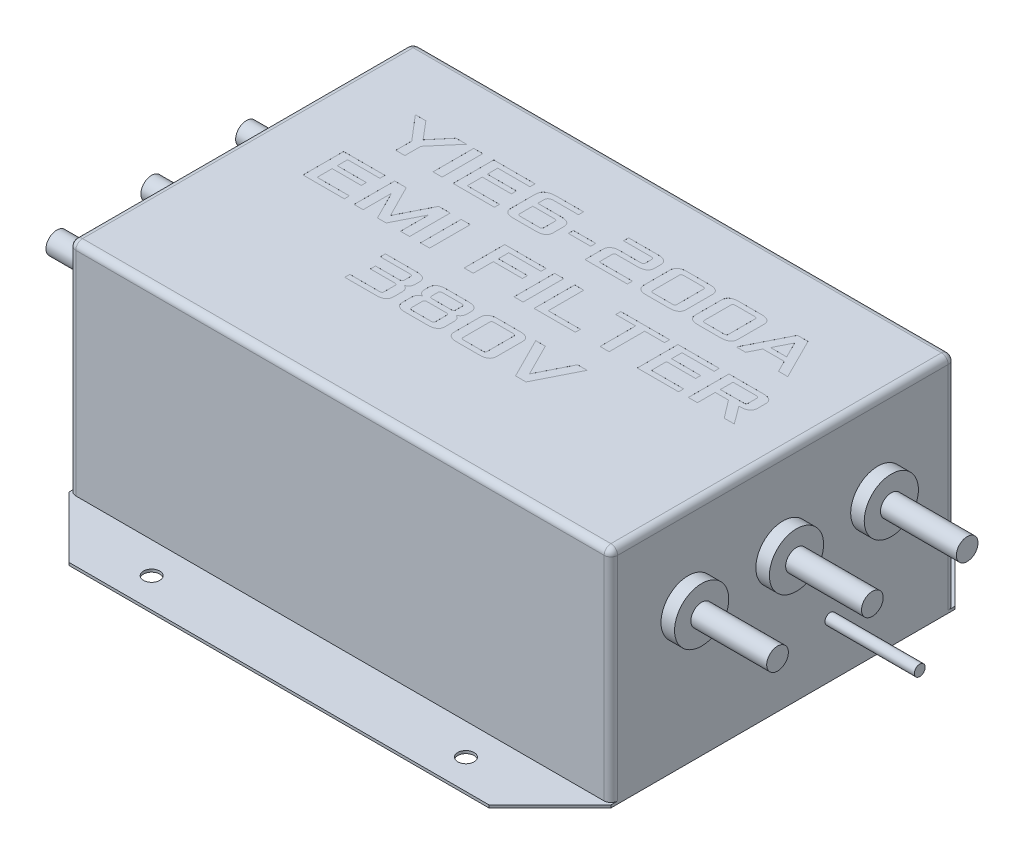
SolidWorks part; units mm, degrees
ref_plane "Front Plane" through (0, 0, 0) normal (0, 0, 1) x (1, 0, 0)
ref_plane "Top Plane" through (0, 0, 0) normal (0, 1, 0) x (1, 0, 0)
ref_plane "Right Plane" through (0, 0, 0) normal (1, 0, 0) x (0, 0, -1)
sketch "Sketch1" plane through (0, 0, 0) normal (0, 1, 0) x (1, 0, 0)
  line L0 (-100, 63.5) -> (-73.8372, 63.5) construction
  line L1 (-77.5, 86) -> (77.5, 86)
  line L2 (-100, 63.5) -> (-100, -63.5)
  line L3 (-77.5, -86) -> (77.5, -86)
  line L4 (100, 63.5) -> (100, -63.5)
  line L5 (-73.8372, 63.5) -> (0, 0) construction
  line L6 (-73.8372, -63.5) -> (73.8372, 63.5) construction
  line L7 (-111.5475, 0) -> (111.5475, 0) construction
  line L8 (73.8372, -63.5) -> (100, -63.5) construction
  line L9 (-100, 63.5) -> (-77.5, 86)
  line L10 (0, 63.5) -> (0, 139.8878) construction
  line L11 (100, 63.5) -> (77.5, 86)
  line L12 (100, -63.5) -> (77.5, -86)
  line L13 (-100, -63.5) -> (-77.5, -86)
  line L14 (-100, 86) -> (-77.5, 86) construction
  line L15 (-100, 86) -> (-87.9032, 75.5968) construction
  line L16 (-100, 86) -> (-100, 63.5) construction
  line L17 (77.5, 86) -> (100, 86) construction
  line L18 (87.9032, 75.5968) -> (100, 86) construction
  line L19 (100, 86) -> (100, 63.5) construction
  line L20 (87.9032, -75.5968) -> (100, -86) construction
  line L21 (77.5, -86) -> (100, -86) construction
  line L22 (-100, -86) -> (-87.9032, -75.5968) construction
  line L23 (-100, -63.5) -> (-100, -86) construction
  line L24 (-100, -63.5) -> (-73.8372, -63.5) construction
  line L25 (-87.9032, -75.5968) -> (-73.8372, -63.5) construction
  line L26 (-73.8372, -63.5) -> (73.8372, -63.5) construction
  line L27 (0, 0) -> (73.8372, -63.5) construction
  line L28 (73.8372, -63.5) -> (87.9032, -75.5968) construction
  line L29 (73.8372, 63.5) -> (100, 63.5) construction
  line L30 (73.8372, 63.5) -> (87.9032, 75.5968) construction
  line L31 (0, 63.5) -> (73.8372, 63.5) construction
  line L32 (0, 0) -> (0, 63.5) construction
  line L33 (-73.8372, 63.5) -> (0, 63.5) construction
  line L34 (-87.9032, 75.5968) -> (-73.8372, 63.5) construction
  line L35 (100, -63.5) -> (100, -86) construction
  line L36 (-100, -86) -> (-77.5, -86) construction
  circle A0 centre (-58, 75) radius 3
  circle A1 centre (58, 75) radius 3
  circle A2 centre (58, -75) radius 3
  circle A3 centre (-58, -75) radius 3
  point P0 (0, 0)
  point P11 (0, 0)
  dimension "D5" = 150
  dimension "D7" = 6
  dimension "D1" = 172
  dimension "D2" = 200
  dimension "D3" = 127
  dimension "D4" = 45
  dimension "D6" = 116
extrude "Boss-Extrude1" add sketch "Sketch1" along normal blind 1
sketch "Sketch2" plane through (0, 1, 0) normal (0, 1, 0) x (1, 0, 0)
  line L1 (100, -63.5) -> (-100, -63.5)
  line L2 (100, -63.5) -> (100, 63.5)
  line L3 (100, 63.5) -> (-100, 63.5)
  line L4 (-100, -63.5) -> (-100, 63.5)
  line L5 (100, -63.5) -> (-100, 63.5) construction
  line L6 (100, 63.5) -> (-100, -63.5) construction
  point P0 (0, 0)
extrude "Boss-Extrude2" add sketch "Sketch2" along normal blind 81
fillet "Fillet3" radius 2.5 8 edges at (0, 82, -63.5) (100, 82, 0) (0, 82, 63.5) (-100, 82, 0) (-100, 41.5, 63.5) (-100, 41.5, -63.5) (100, 41.5, -63.5) (100, 41.5, 63.5) tangent propagation no
sketch "Sketch3" plane through (0, 0, 0) normal (1, 0, 0) x (0, 0, -1)
  line L0 (0, 0) -> (0, 94.6087) construction
  line L1 (-63.5, 0) -> (63.5, 0) construction
  line L3 (0, 50) -> (35, 50) construction
  circle A0 centre (-35, 50) radius 4
  circle A1 centre (35, 50) radius 4
  circle A2 centre (0, 50) radius 4
  circle A3 centre (17.5, 20) radius 2
  point P6 (17.5, 50)
  dimension "D1" = 50
  dimension "D3" = 8
  dimension "D4" = 8
  dimension "D5" = 4
  dimension "D2" = 70
  dimension "D6" = 20
extrude "Boss-Extrude3" add sketch "Sketch3" along normal blind 133
extrude "Boss-Extrude4" add sketch "Sketch3<2>" against normal blind 133 contours A0 | A2 | A1
sketch "Sketch3<2>" plane through (0, 0, 0) normal (1, 0, 0) x (0, 0, -1) same geometry as "Sketch3"
sketch "Sketch4" plane through (0, 82, 0) normal (0, 1, 0) x (1, 0, 0)
  line L0 (-75.9725, 25) -> (75.9725, 25) construction
  line L1 (-75.9725, -25) -> (75.9725, -25) construction
  line L2 (-78.8588, 0) -> (75.9725, 0) construction
  text T0 "YIE6-200A" font "Xolonium" height 15
  text T1 "380V" font "Xolonium" height 15
  text T2 "EMI FILTER" font "Xolonium" height 15
  point P3 (0, 25)
  point P10 (75.9725, 0)
  point P11 (-75.9725, 0)
  point P12 (-89.2878, 0)
  point P13 (-82.8049, 0)
  point P14 (-78.8588, 0)
  dimension "D1" = 25
  dimension "D2" = 25
  dimension "D3" = 25
extrude "Cut-Extrude1" cut sketch "Sketch4" against normal blind 0.01
sketch "Sketch5" plane through (0, 0, 0) normal (1, 0, 0) x (0, 0, -1)
  circle A0 centre (-35, 50) radius 10
  circle A1 centre (0, 50) radius 10
  circle A2 centre (35, 50) radius 10
  point P7 (35, 50)
  point P9 (0, 50)
  point P10 (0, 0)
  dimension "D1" = 20
extrude "Boss-Extrude5" add sketch "Sketch5" along normal mid plane 210
